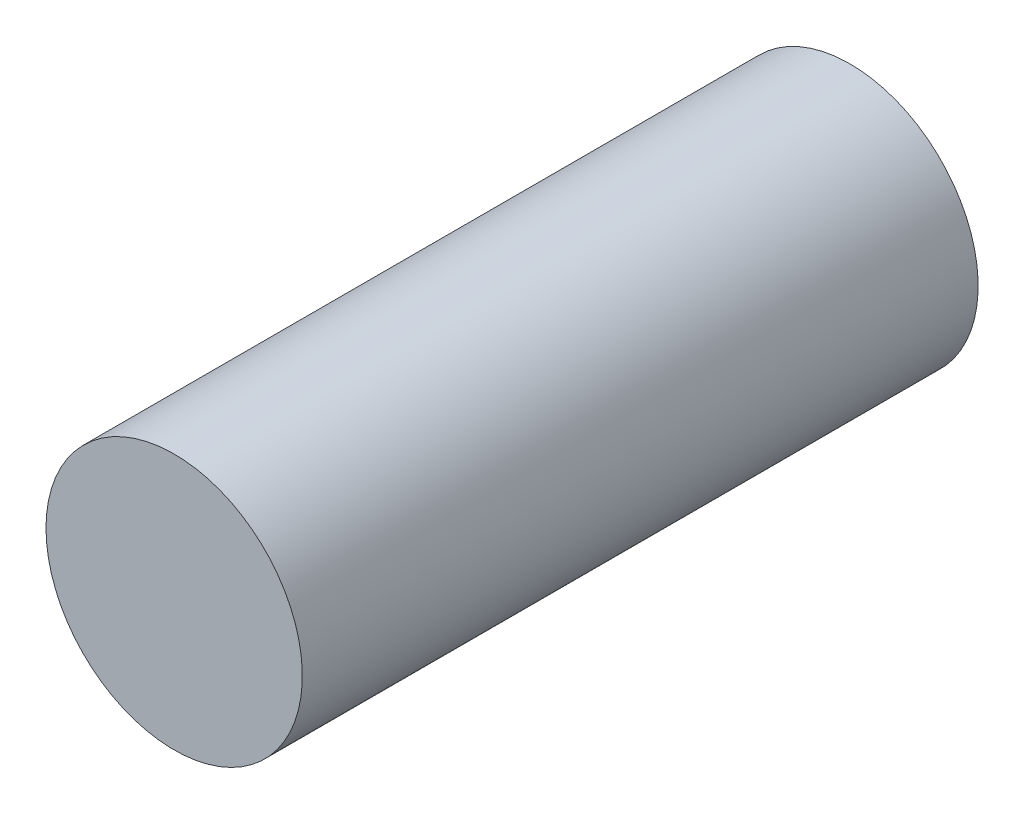
SolidWorks part; units mm, degrees
ref_plane "Front Plane" through (0, 0, 0) normal (0, 0, 1) x (1, 0, 0)
ref_plane "Top Plane" through (0, 0, 0) normal (0, 1, 0) x (1, 0, 0)
ref_plane "Right Plane" through (0, 0, 0) normal (1, 0, 0) x (0, 0, -1)
sketch "Sketch1" plane through (0, 0, 0) normal (0, 0, 1) x (1, 0, 0)
  circle A0 centre (-17.0971, 11.9612) radius 5.5
extrude "Boss-Extrude1" add sketch "Sketch1" along normal blind 29
